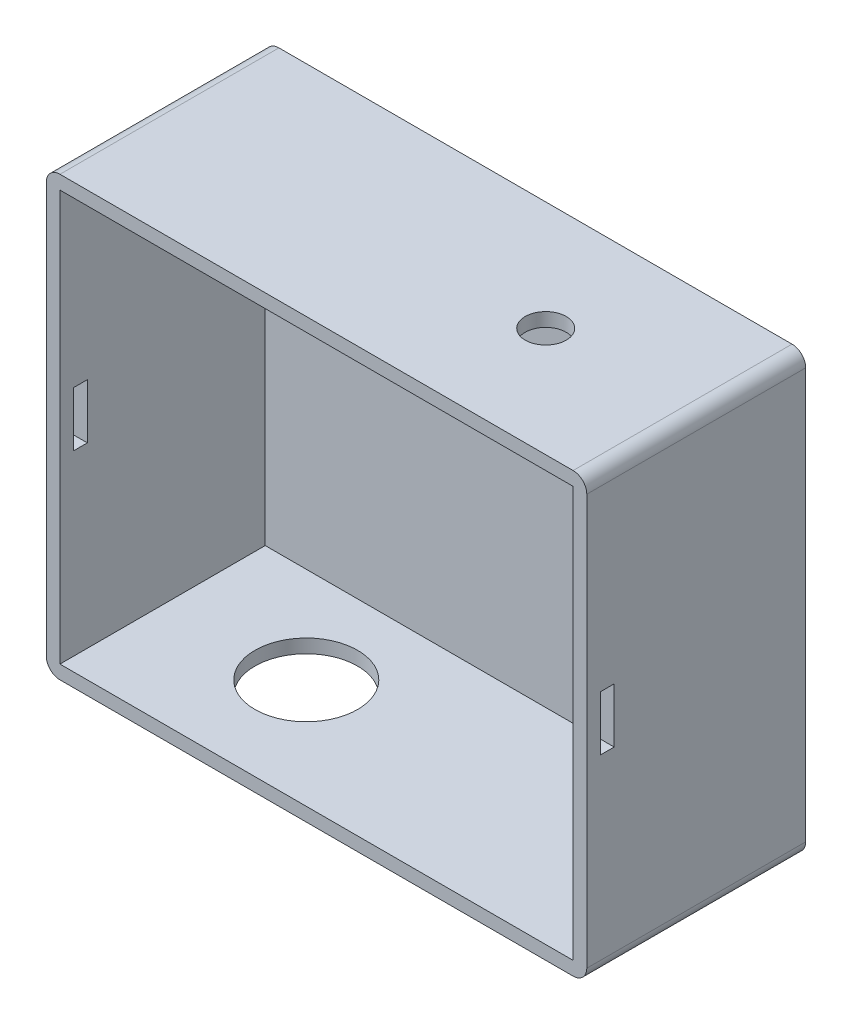
SolidWorks part; units mm, degrees
ref_plane "前视基准面" through (0, 0, 0) normal (0, 0, 1) x (1, 0, 0)
ref_plane "上视基准面" through (0, 0, 0) normal (0, 1, 0) x (1, 0, 0)
ref_plane "右视基准面" through (0, 0, 0) normal (1, 0, 0) x (0, 0, -1)
other "Configuration Table"
sketch "外壳基体" plane through (0, 0, 0) normal (0, 0, 1) x (1, 0, 0)
  line L0 (-39.5, -32) -> (-39.5, 32)
  line L1 (-37.5, -30) -> (37.5, -30)
  line L2 (-37.5, -30) -> (-37.5, 30)
  line L3 (-37.5, 30) -> (37.5, 30)
  line L4 (37.5, -30) -> (37.5, 30)
  line L5 (-37.5, -30) -> (37.5, 30) construction
  line L6 (-37.5, 30) -> (37.5, -30) construction
  line L7 (-39.5, 32) -> (39.5, 32)
  line L8 (39.5, -32) -> (39.5, 32)
  line L9 (-39.5, -32) -> (39.5, -32)
  point P0 (0, 0)
  dimension "D1" = 60
  dimension "D2" = 75
  dimension "D3" = 2
extrude "外壳边框" add sketch "外壳基体" along normal blind 30
extrude "外壳底部" add sketch "外壳基体<3>" against normal blind 2 contours L1 L4 L3 L2 | L0 L9 L8 L7 L4 L1 L2 L3 region at (-38.4833, 0, 0) region at (0, 0, 0)
sketch "外壳基体<3>" plane through (0, 0, 0) normal (0, 0, 1) x (1, 0, 0) same geometry as "外壳基体"
sketch "草图3" plane through (0, 0, 0) normal (0, 1, 0) x (1, 0, 0)
  line L0 (-39.5, -14) -> (-17.5, -14) construction
  line L1 (-39.5, -30) -> (-39.5, 2) construction
  line L2 (39.5, -14) -> (17.5, -14) construction
  line L3 (39.5, -30) -> (39.5, 2) construction
  circle A0 centre (-17.5, -14) radius 7.5
  circle A1 centre (17.5, -14) radius 3
  dimension "D1" = 15
extrude "线槽" cut sketch "草图3" along normal blind 2 from surface contours A0 region at (-17.5, 0, 14) starting at face at (0, -32, 14)
extrude "天线" cut sketch "草图3<3>" against normal blind 2 from surface contours A1 region at (17.5, 0, 14) starting at face at (0, 32, 14)
sketch "草图3<3>" plane through (0, 0, 0) normal (0, 1, 0) x (1, 0, 0) same geometry as "草图3"
sketch "草图4" plane through (0, 0, 0) normal (1, 0, 0) x (0, 0, -1)
  line L0 (-30, 0) -> (-27, 0) construction
  line L1 (-30, -32) -> (-30, 32) construction
  line L3 (-26, -4) -> (-28, -4)
  line L4 (-26, -4) -> (-26, 4)
  line L5 (-26, 4) -> (-28, 4)
  line L6 (-28, -4) -> (-28, 4)
  line L7 (-26, -4) -> (-28, 4) construction
  line L8 (-26, 4) -> (-28, -4) construction
  dimension "D1" = 2
  dimension "D2" = 8
  dimension "D3" = 3
extrude "盖子扣槽" cut sketch "草图4" against normal through all both and the other way through all
fillet "外边框圆角" radius 2 4 edges at (-39.5, -32, 14) (39.5, -32, 14) (-39.5, 32, 14) (39.5, 32, 14)
